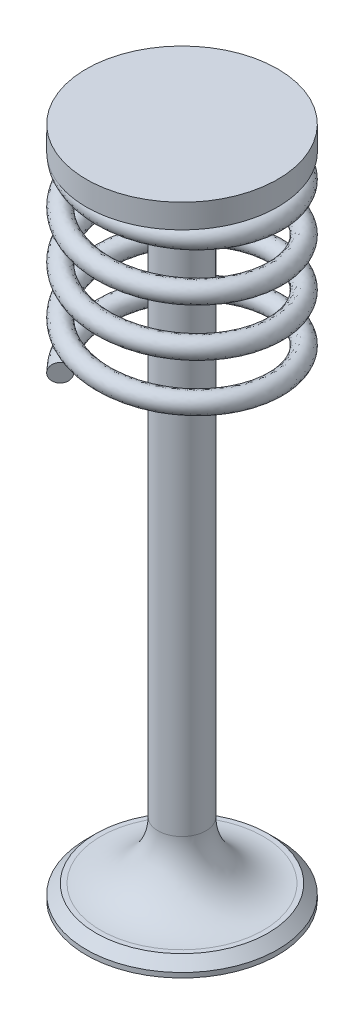
SolidWorks part; units mm, degrees
material "Alloy Steel (SS)"
ref_plane "Front Plane" through (0, 0, 0) normal (0, 0, 1) x (1, 0, 0)
ref_plane "Top Plane" through (0, 0, 0) normal (0, 1, 0) x (1, 0, 0)
ref_plane "Right Plane" through (0, 0, 0) normal (1, 0, 0) x (0, 0, -1)
sketch "Sketch1" plane through (0, 0, 0) normal (0, 0, 1) x (1, 0, 0)
  line L0 (10, 0) -> (0, 0)
  line L1 (0, 0) -> (0, 70.2)
  line L2 (0, 70.2) -> (10, 70.2)
  line L4 (10, 0) -> (10, 0.5)
  line L5 (10, 0.5) -> (9, 1.5)
  line L6 (9, 1.5) -> (8.5, 1.5)
  line L9 (10, 70.2) -> (10, 67.7)
  line L10 (10, 67.7) -> (2.5, 67.7)
  line L11 (2.5, 67.7) -> (2.5, 7.5)
  arc A0 (2.5, 7.5) -> (8.5, 1.5) centre (8.5, 7.5) ccw
  dimension "D1" = 10
  dimension "D2" = 2.5
  dimension "D3" = 0.5
  dimension "D4" = 1.5
  dimension "D5" = 45
  dimension "D6" = 0.5
  dimension "D7" = 70.2
  dimension "D8" = 10
  dimension "D10" = 2.5
revolve "Revolve1" add sketch "Sketch1" angle 360 about L1
sketch "Sketch2" plane through (0, 67.7, 0) normal (0, -1, 0) x (1, 0, 0)
  circle A0 centre (0, 0) radius 9
  dimension "D1" = 18
curve "Helix/Spiral1" pitch 5 height 20 turns 4
sweep "Sweep1" add path "Helix/Spiral1" circular profile diameter 2 parameters "D3"=2
